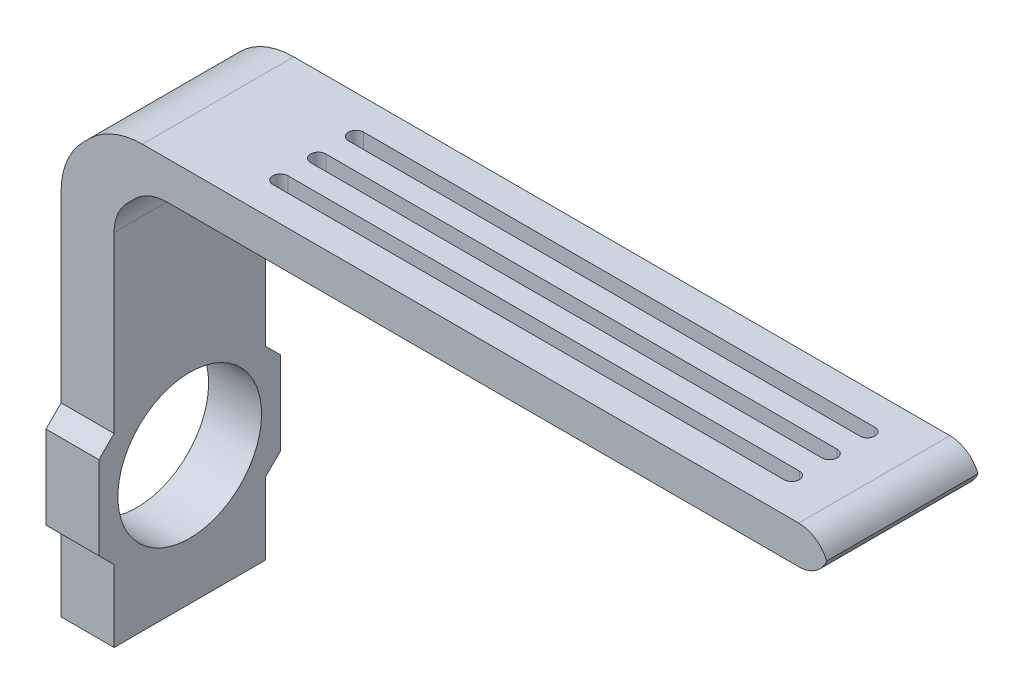
SolidWorks part; units mm, degrees
ref_plane "Front Plane" through (0, 0, 0) normal (0, 0, 1) x (1, 0, 0)
ref_plane "Top Plane" through (0, 0, 0) normal (0, 1, 0) x (1, 0, 0)
ref_plane "Right Plane" through (0, 0, 0) normal (1, 0, 0) x (0, 0, -1)
sketch "Sketch1" plane through (0, 0, 0) normal (0, 0, 1) x (1, 0, 0)
  line L0 (-47.5533, 5.01) -> (-47.5533, 0.01)
  line L8 (-142.4528, 5.01) -> (-47.5533, 5.01)
  line L9 (-149.0533, -1.5905) -> (-142.4528, 5.01)
  line L10 (-149.0533, -54.49) -> (-149.0533, -1.5905)
  line L11 (-142.0533, -54.49) -> (-149.0533, -54.49)
  line L12 (-142.0533, -4.49) -> (-142.0533, -54.49)
  line L13 (-137.5533, 0.01) -> (-142.0533, -4.49)
  line L14 (-47.5533, 0.01) -> (-137.5533, 0.01)
  point P2 (0, 0)
  dimension "D1" = 90
  dimension "D2" = 5
  dimension "D3" = 50
  dimension "D4" = 7
  dimension "D5" = 7
  dimension "D6" = 135
  dimension "D7" = 4.5
extrude "Boss-Extrude1" add sketch "Sketch1" along normal blind 20
fillet "Fillet1" radius 6 2 edges at (-137.5533, 0.01, 10) (-142.0533, -4.49, 10)
sketch "Sketch2" plane through (0, 0.01, 0) normal (0, -1, 0) x (-1, 0, 0)
  line L0 (47.5533, -20) -> (47.5533, 0) construction
  line L1 (135.0681, -20) -> (135.0681, 0) construction
  line L2 (135.0681, -10) -> (125.0681, -10) construction
  line L3 (47.5533, -10) -> (57.4615, -10) construction
  line L4 (125.0681, -10) -> (57.4615, -10) construction
  line L5 (125.0681, -11) -> (57.4615, -11)
  line L6 (125.0681, -9) -> (57.4615, -9)
  line L7 (125.0681, -4) -> (57.4615, -4)
  line L10 (125.0681, -6) -> (57.4615, -6)
  line L13 (125.0681, -5) -> (57.4615, -5) construction
  line L14 (125.0681, -15) -> (57.4615, -15) construction
  line L15 (125.0681, -16) -> (57.4615, -16)
  line L16 (125.0681, -14) -> (57.4615, -14)
  arc A0 (125.0681, -11) -> (125.0681, -9) centre (125.0681, -10) ccw
  arc A1 (57.4615, -9) -> (57.4615, -11) centre (57.4615, -10) ccw
  arc A6 (125.0681, -6) -> (125.0681, -4) centre (125.0681, -5) ccw
  arc A7 (57.4615, -4) -> (57.4615, -6) centre (57.4615, -5) ccw
  arc A8 (125.0681, -16) -> (125.0681, -14) centre (125.0681, -15) ccw
  arc A9 (57.4615, -14) -> (57.4615, -16) centre (57.4615, -15) ccw
  point P12 (91.2648, -10)
  point P21 (91.2648, -5)
  point P27 (91.2648, -15)
  dimension "D1" = 2
  dimension "D2" = 2
extrude "Cut-Extrude1" cut sketch "Sketch2" against normal up to surface (5 mm away) up to face at (-95.0031, 5.01, 10)
fillet "Fillet3" radius 4 2 edges at (-47.5533, 5.01, 10) (-47.5533, 0.01, 10)
fillet "Fillet2" radius 10 2 edges at (-149.0533, -1.5905, 10) (-142.4528, 5.01, 10)
sketch "Sketch3" plane through (-142.0533, 0, 0) normal (1, 0, 0) x (0, 0, -1)
  line L2 (-10, -6.9753) -> (-10, -37.4853) construction
  line L3 (0, -6.9753) -> (-20, -6.9753) construction
  circle A6 centre (-10, -37.4853) radius 9.5
extrude "Cut-Extrude2" cut sketch "Sketch3" against normal up to surface (7 mm away) up to face at (-149.0533, -30.1113, 10)
sketch "Sketch5" plane through (0, 0, 20) normal (0, 0, 1) x (1, 0, 0)
  line L0 (-142.0533, -6.9753) -> (-149.0533, -6.9753) construction
  line L1 (-149.0533, -5.7326) -> (-149.0533, -54.49) construction
  line L2 (-145.5533, -6.9753) -> (-145.5533, -37.4853) construction
  line L3 (-142.0533, -54.49) -> (-142.0533, -6.9753) construction
  line L4 (-149.0533, -44.9853) -> (-142.0533, -44.9853)
  line L5 (-149.0533, -44.9853) -> (-149.0533, -29.9853)
  line L6 (-149.0533, -29.9853) -> (-142.0533, -29.9853)
  line L7 (-142.0533, -44.9853) -> (-142.0533, -29.9853)
  line L8 (-149.0533, -44.9853) -> (-142.0533, -29.9853) construction
  line L9 (-149.0533, -29.9853) -> (-142.0533, -44.9853) construction
extrude "Boss-Extrude3" add sketch "Sketch5" along normal blind 2
sketch "Sketch6" plane through (0, 0, 0) normal (0, 0, -1) x (-1, 0, 0)
  line L0 (142.0533, -6.9753) -> (149.0533, -6.9753) construction
  line L1 (149.0533, -5.7326) -> (149.0533, -54.49) construction
  line L2 (145.5533, -6.9753) -> (145.5533, -37.4853) construction
  line L3 (142.0533, -54.49) -> (142.0533, -6.9753) construction
  line L4 (149.0533, -44.9853) -> (142.0533, -44.9853)
  line L5 (149.0533, -44.9853) -> (149.0533, -29.9853)
  line L6 (149.0533, -29.9853) -> (142.0533, -29.9853)
  line L7 (142.0533, -44.9853) -> (142.0533, -29.9853)
  line L8 (149.0533, -44.9853) -> (142.0533, -29.9853) construction
  line L9 (149.0533, -29.9853) -> (142.0533, -44.9853) construction
extrude "Boss-Extrude4" add sketch "Sketch6" along normal blind 2
chamfer "Chamfer1" distance 2 angle 45 4 edges at (-145.5533, -29.9853, 22) (-145.5533, -44.9853, 22) (-145.5533, -29.9853, -2) (-145.5533, -44.9853, -2)
